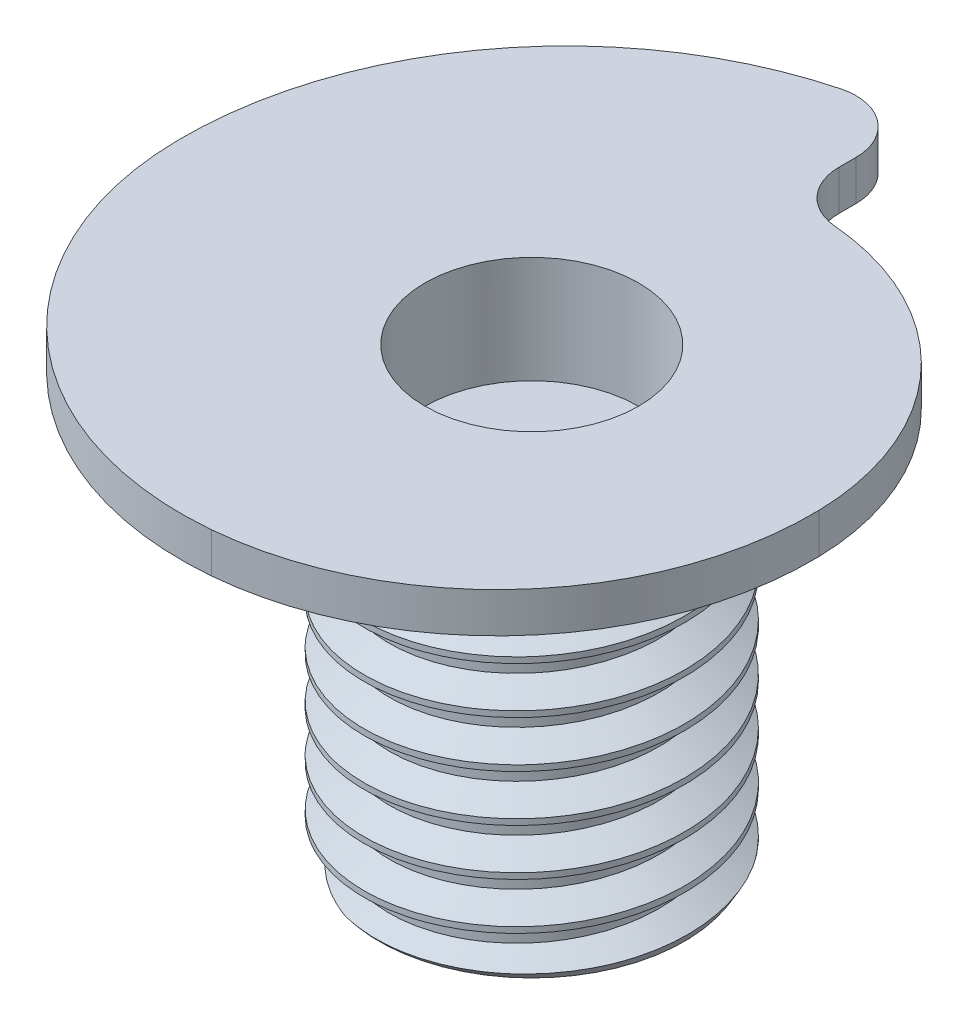
SolidWorks part; units mm, degrees
ref_plane "Front Plane" through (0, 0, 0) normal (0, 0, 1) x (1, 0, 0)
ref_plane "Top Plane" through (0, 0, 0) normal (0, 1, 0) x (1, 0, 0)
ref_plane "Right Plane" through (0, 0, 0) normal (1, 0, 0) x (0, 0, -1)
sketch "Sketch1" plane through (0, 0, 0) normal (1, 0, 0) x (0, 0, -1)
  line L2 (17, 30) -> (17, 26.5)
  line L3 (17, 26.5) -> (12, 26.5)
  line L4 (12, 23.825) -> (12, 0)
  line L6 (0, 0) -> (0, 30) construction
  line L7 (17, 30) -> (8, 30)
  line L8 (8, 30) -> (8, 25)
  line L9 (8, 25) -> (3, 25)
  line L10 (3, 25) -> (3, 5)
  line L11 (3, 5) -> (8, 5)
  line L12 (8, 5) -> (8, 0)
  line L13 (8, 0) -> (12, 0)
  line L14 (12, 26.5) -> (12, 23.825)
  dimension "D1" = 8
  dimension "D2" = 6
  dimension "D3" = 5
  dimension "D4" = 17
  dimension "D5" = 3.5
  dimension "D6" = 30
  dimension "D7" = 12
  dimension "D8" = 5
revolve "Revolve1" add sketch "Sketch1" angle 360 about L6
chamfer "Chamfer1" distance 1 angle 30 1 edges at (0, 0, -12) first distance on face at (0, 26.5, -12)
thread "Thread1" pitch 3.5 method cut profile "Thread Profile1" start angle 0, offset 0, length 26, pitch 3.5, diameter 24
ref_plane "Plane1" through (-12, 26.5, 0) normal (0, 0, 1) x (-1, 0, 0)
sketch "Thread Profile1" plane through (-12, 26.5, 0) normal (0, 0, 1) x (-1, 0, 0)
  line L0 (0, 0) -> (0, 3.5) construction
  line L11 (0, 0) -> (0, 3.0625)
  line L12 (0, 3.0625) -> (-1.8944, 1.9687)
  line L13 (-1.8944, 1.9687) -> (-1.8944, 1.0937)
  line L15 (-1.8944, 1.0937) -> (0, 0)
  line L17 (-1.8944, 1.5312) -> (0, 1.5312) construction
  point P2 (0, 0)
  dimension "Pitch" = 3.5
  dimension "Profile_Angle" = 60
  dimension "Profile_Land" = 0.875
  dimension "Profile_Height" = 1.8944
sketch "Sketch2" plane through (0, 30, 0) normal (0, 1, 0) x (1, 0, 0)
  line L1 (0, 11.547) -> (-10, -5.7735) construction
  line L2 (-10, -5.7735) -> (10, -5.7735) construction
  line L3 (10, -5.7735) -> (0, 11.547) construction
  circle A0 centre (0, 0) radius 5.7735 construction
  circle A1 centre (0, 11.547) radius 1.5
  circle A2 centre (10, -5.7735) radius 1.5
  circle A3 centre (-10, -5.7735) radius 1.5
  dimension "D2" = 3
  dimension "D1" = 20
extrude "Cut-Extrude1" [suppressed] cut sketch "Sketch2" against normal blind 4
sketch "Sketch3" plane through (0, 30, 0) normal (0, 1, 0) x (1, 0, 0)
  line L0 (0, 29) -> (0, -29) construction
  line L1 (-29, 0) -> (29, 0) construction
  line L2 (0, 29) -> (0, 19)
  circle A1 centre (0, 0) radius 19 construction
  circle A2 centre (0, 0) radius 21.5 construction
  circle A3 centre (0, 0) radius 24 construction
  circle A4 centre (0, 0) radius 26.5 construction
  circle A5 centre (0, 0) radius 29 construction
  arc A6 (0, 29) -> (-26.5, 0) centre (2.2755, 0.3129) ccw
  arc A7 (-26.5, 0) -> (0, -24) centre (-2.1422, 0.2649) ccw
  arc A8 (0, -24) -> (21.5, 0) centre (-2.0736, -0.5122) ccw
  arc A9 (21.5, 0) -> (0, 19) centre (1.9798, -0.4242) ccw
  point P24 (-27.5, 0)
  dimension "D1" = 38
  dimension "D2" = 2.5
  dimension "D3" = 2.5
  dimension "D4" = 2.5
  dimension "D5" = 2.5
extrude "Boss-Extrude1" add sketch "Sketch3" along normal blind 3
sketch "Sketch4" plane through (0, 33, 0) normal (0, 1, 0) x (1, 0, 0)
  circle A0 centre (0, 0) radius 8 construction
  circle A1 centre (0, 0) radius 8
extrude "Cut-Extrude2" cut sketch "Sketch4" against normal blind 6
fillet "Fillet1" radius 4 2 edges at (0, 31.5, -19) (0, 31.5, -29)
